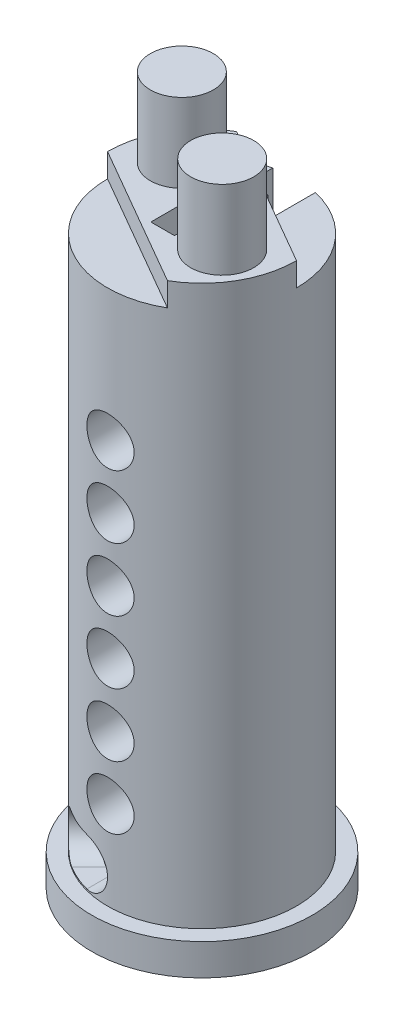
SolidWorks part; units mm, degrees
ref_plane "前视基准面" through (0, 0, 0) normal (0, 0, 1) x (1, 0, 0)
ref_plane "上视基准面" through (0, 0, 0) normal (0, 1, 0) x (1, 0, 0)
ref_plane "右视基准面" through (0, 0, 0) normal (1, 0, 0) x (0, 0, -1)
other "Configuration Table"
sketch "草图1" plane through (0, 0, 0) normal (0, 1, 0) x (1, 0, 0)
  circle A0 centre (0, 0) radius 7
  dimension "D1" = 14
extrude "凸台-拉伸1" add sketch "草图1" along normal blind 2
sketch "草图2" plane through (0, 2, 0) normal (0, 1, 0) x (1, 0, 0)
  circle A0 centre (0, 0) radius 6
  dimension "D1" = 12
extrude "凸台-拉伸2" add sketch "草图2" along normal blind 35.5
sketch "草图3" plane through (0, 37.5, 0) normal (0, 1, 0) x (1, 0, 0)
  line L0 (-3.0311, 1.75) -> (0, 0)
  line L1 (0, 0) -> (3.0311, -1.75)
  line L2 (-3.9722, 5.7574) -> (7.138, -0.657)
  line L3 (-2.9038, 0) -> (1.9443, 0) construction
  line L4 (-6.9722, 0.5613) -> (4.138, -5.8532)
  circle A0 centre (0, 0) radius 3.5
  circle A1 centre (-3.0311, 1.75) radius 2
  circle A2 centre (3.0311, -1.75) radius 2
  circle A3 centre (0, 0) radius 6 construction
  circle A4 centre (0, 0) radius 6
  circle M7 centre (0, 0) radius 6
  dimension "D2" = 7
  dimension "D3" = 4
  dimension "D1" = 3
  dimension "D4" = 30
extrude "切除-拉伸1" cut sketch "草图3" against normal blind 1.5 and the other way through all contours L4 A0 | A0 L4 M7 | A0 L2 M7 | L2 A0 region at (1.6006, 37.5, -2.7724) region at (2.1451, 37.5, -3.7154) region at (-2.1451, 37.5, 3.7154) region at (-1.6006, 37.5, 2.7724)
sketch "草图4" plane through (0, 37.5, 0) normal (0, 1, 0) x (1, 0, 0)
  circle A0 centre (3.0311, -1.75) radius 2 construction
  circle A1 centre (3.0311, -1.75) radius 2
  circle A2 centre (-3.0311, 1.75) radius 2 construction
  circle A3 centre (-3.0311, 1.75) radius 2
extrude "凸台-拉伸3" add sketch "草图4" along normal blind 5
sketch "草图5" plane through (0, 0, 0) normal (0, 1, 0) x (1, 0, 0)
  line L0 (0, -0.0947) -> (0, 7) construction
  line L1 (-1.35, 6.8686) -> (-1.35, 4.2)
  line L2 (-1.35, 4.2) -> (0, 4.2)
  line L3 (0, 4.2) -> (0, 2.7)
  line L4 (0, 2.7) -> (-0.75, 2.7)
  line L5 (-0.75, 2.7) -> (-0.75, -2.5)
  line L6 (-0.75, -2.5) -> (0.75, -2.5)
  line L7 (0.75, -2.5) -> (0.75, 1.5)
  line L8 (0.75, 1.5) -> (1.3534, 1.5)
  line L9 (1.3534, 1.5) -> (1.3534, 6.8679)
  line L10 (0, 7) -> (3.4516, 7) construction
  circle A0 centre (0, 0) radius 7 construction
  circle A1 centre (0, 0) radius 7
  dimension "D4" = 0.75
  dimension "D3" = 1.5
  dimension "D5" = 0.75
  dimension "D1" = 2.8
  dimension "D2" = 2.7034
  dimension "D6" = 1.35
  dimension "D7" = 5.5
  dimension "D8" = 9.5
extrude "切除-拉伸2" cut sketch "草图5" against normal through all both and the other way through all contours L1 L2 L3 L4 L5 L6 L7 L8 L9
sketch "草图13" plane through (0, 0, 0) normal (0, 0, 1) x (1, 0, 0)
  line L0 (0, 0) -> (0, 27.6) construction
  line L1 (-7, 0) -> (7, 0) construction
  circle A0 centre (0, 27.6) radius 1.5
  dimension "D1" = 3
  dimension "D2" = 27.6
extrude "切除-拉伸6" cut sketch "草图13" against normal up to surface (1.5 mm away) and the other way through all from offset 40 contours A0 up to face at (1.0517, 18.75, -1.5)
sketch "草图14" plane through (0, 0, 0) normal (0, 0, 1) x (1, 0, 0)
  line L0 (0, 27.6) -> (0, 3.5623) construction
  line L1 (0, 37.5) -> (0, 0) construction
pattern_linear "阵列(线性)2" count 6 spacing 4 along (0, -1, 0) of "切除-拉伸6"
ref_plane "基准面1" through (0, 3.6, 0) normal (0, 1, 0) x (1, 0, 0)
sketch "草图15" plane through (0, 3.6, 0) normal (0, 1, 0) x (1, 0, 0)
  line L0 (0, -4.5) -> (0, -6.3553)
  line L1 (-3.304, -3.0551) -> (-4.3652, -4.1164)
  arc A0 (-3.304, -3.0551) -> (0, -4.5) centre (0, 0) ccw
  arc A1 (-1.35, 5.8462) -> (1.3534, 5.8454) centre (0, 0) ccw construction
  arc A2 (-4.3652, -4.1164) -> (0, -6) centre (0, 0) ccw
  dimension "D1" = 9
  dimension "D2" = 45
extrude "切除-拉伸7" cut sketch "草图15" against normal mid plane 3 contours L1 A2 L0 A0 region at (-2.045, 3.6, 4.7134)
fillet "圆角2" 2 edges at (0, 2.1, 5.25) (0, 5.1, 5.25) type full round first side face at (-2.0037, 2.1, 4.6169) second side face at (-2.0037, 5.1, 4.6169) middle face at (0, 3.6, 5.25)
fillet "圆角3" 2 edges at (-3.8346, 5.1, 3.5857) (-3.8346, 2.1, 3.5857) type full round first side face at (-2.7153, 5.1, 4.384) second side face at (-2.7153, 2.1, 4.384) middle face at (-3.8346, 3.6, 3.5857)
